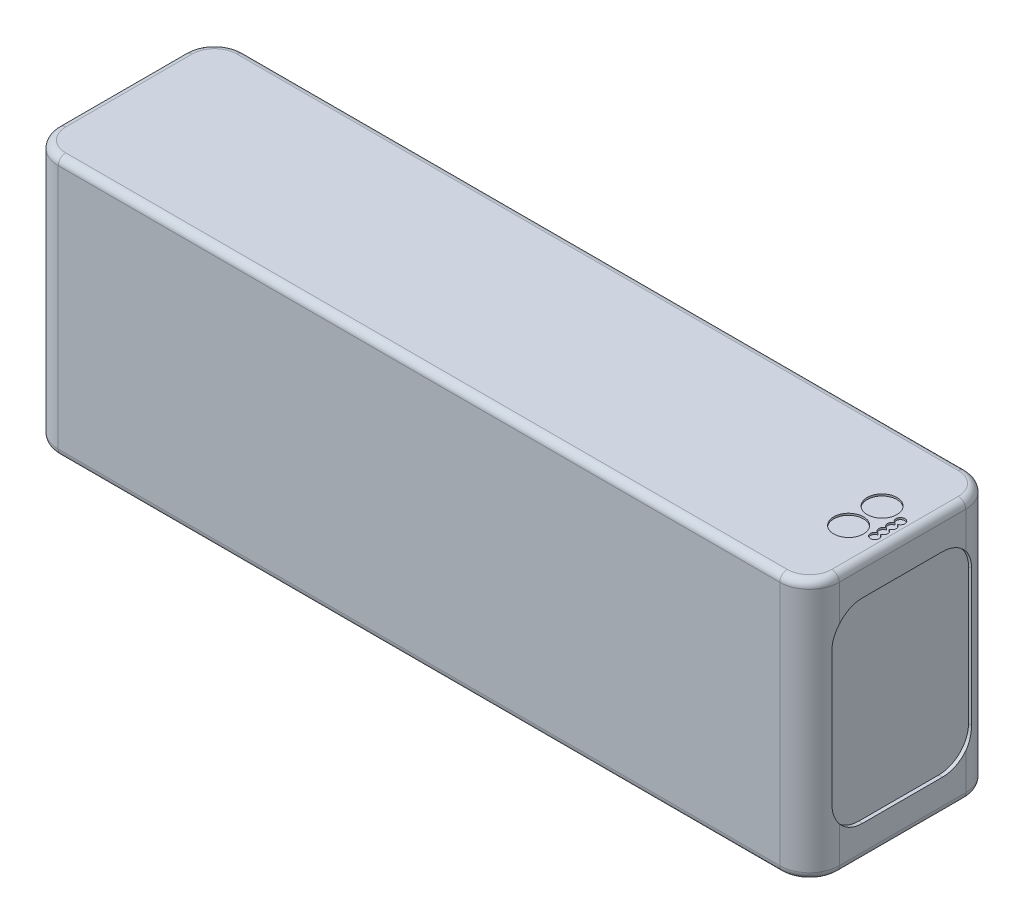
SolidWorks part; units mm, degrees
ref_plane "Front Plane" through (0, 0, 0) normal (0, 0, 1) x (1, 0, 0)
ref_plane "Top Plane" through (0, 0, 0) normal (0, 1, 0) x (1, 0, 0)
ref_plane "Right Plane" through (0, 0, 0) normal (1, 0, 0) x (0, 0, -1)
ref_plane "Plane1" through (0, 0, -15) normal (0, 0, -1) x (-1, 0, 0)
sketch "Sketch1" plane through (0, 0, -15) normal (0, 0, -1) x (-1, 0, 0)
  line L0 (-52.5, -17.5) -> (52.5, -17.5)
  line L1 (52.5, -17.5) -> (52.5, 17.5)
  line L2 (52.5, 17.5) -> (-52.5, 17.5)
  line L3 (-52.5, 17.5) -> (-52.5, -17.5)
  line L4 (-52.5, 0) -> (52.5, 0) construction
  line L5 (0, 17.5) -> (0, -17.5) construction
  dimension "D1" = 35
  dimension "D2" = 105
extrude "Boss-Extrude1" add sketch "Sketch1" against normal blind 25
sketch "Sketch2" plane through (52.5, 0, 0) normal (1, 0, 0) x (0, 0, -1)
  line L0 (-6.875, 9.125) -> (-6.875, -9.125)
  line L1 (-2.875, -13.125) -> (7.875, -13.125)
  line L2 (11.875, -9.125) -> (11.875, 9.125)
  line L3 (7.875, 13.125) -> (-2.875, 13.125)
  line L4 (-10, 17.5) -> (15, -17.5) construction
  line L5 (15, 17.5) -> (-10, -17.5) construction
  line L6 (-6.875, 13.125) -> (11.875, -13.125) construction
  line L7 (11.875, 13.125) -> (-6.875, -13.125) construction
  line L12 (-10, 17.5) -> (15, 17.5) construction
  line L13 (-10, 17.5) -> (-10, -17.5) construction
  line L14 (-10, -17.5) -> (15, -17.5) construction
  line L15 (15, 17.5) -> (15, -17.5) construction
  line L16 (-10, 17.5) -> (15, -17.5) construction
  line L17 (-10, -17.5) -> (15, 17.5) construction
  arc A0 (-6.875, -9.125) -> (-2.875, -13.125) centre (-2.875, -9.125) ccw
  arc A1 (7.875, -13.125) -> (11.875, -9.125) centre (7.875, -9.125) ccw
  arc A2 (11.875, 9.125) -> (7.875, 13.125) centre (7.875, 9.125) ccw
  arc A3 (-6.875, 9.125) -> (-2.875, 13.125) centre (-2.875, 9.125) cw
  point P16 (2.5, 0)
  dimension "D3" = 4
  dimension "D1" = 18.75
  dimension "D2" = 25
extrude "Cut-Extrude1" cut sketch "Sketch2" against normal blind 0.5
sketch "Sketch3" plane through (-52.5, 0, 0) normal (-1, 0, 0) x (0, 0, 1)
  line L0 (2.875, 13.125) -> (-7.875, 13.125)
  line L1 (-11.875, 9.125) -> (-11.875, -9.125)
  line L2 (-7.875, -13.125) -> (2.875, -13.125)
  line L3 (6.875, -9.125) -> (6.875, 9.125)
  line L4 (-11.875, 13.125) -> (6.875, -13.125) construction
  line L5 (6.875, 13.125) -> (-11.875, -13.125) construction
  line L6 (-15, 17.5) -> (10, -17.5) construction
  line L7 (10, -17.5) -> (-15, -17.5) construction
  line L8 (-15, -17.5) -> (10, 17.5) construction
  arc A0 (-11.875, -9.125) -> (-7.875, -13.125) centre (-7.875, -9.125) ccw
  arc A1 (2.875, -13.125) -> (6.875, -9.125) centre (2.875, -9.125) ccw
  arc A2 (2.875, 13.125) -> (6.875, 9.125) centre (2.875, 9.125) cw
  arc A3 (-7.875, 13.125) -> (-11.875, 9.125) centre (-7.875, 9.125) ccw
  dimension "D3" = 4
  dimension "D1" = 18.75
  dimension "D2" = 25
extrude "Cut-Extrude2" cut sketch "Sketch3" against normal blind 0.5
fillet "Fillet1" radius 4 4 edges at (-52.5, 0, -15) (-52.5, 0, 10) (52.5, 0, -15) (52.5, 0, 10) tangent propagation no
fillet "Fillet2" radius 1 16 edges at (51.3284, 17.5, -13.8284) (52.5, 17.5, -2.5) (0, 17.5, -15) (51.3284, 17.5, 8.8284) (-51.3284, 17.5, -13.8284) (0, 17.5, 10) (-52.5, 17.5, -2.5) (-51.3284, 17.5, 8.8284) (-52.5, -17.5, -2.5) (-51.3284, -17.5, -13.8284) (-51.3284, -17.5, 8.8284) (0, -17.5, -15) (0, -17.5, 10) (51.3284, -17.5, -13.8284) (51.3284, -17.5, 8.8284) (52.5, -17.5, -2.5) tangent propagation no
sketch "Sketch4" plane through (0, 0, 10) normal (0, 0, 1) x (1, 0, 0)
  line L0 (-48.5, 0) -> (48.5, 0) construction
  line L1 (-48.5, 16.5) -> (-48.5, -16.5) construction
  line L2 (48.5, -16.5) -> (48.5, 16.5) construction
  line L3 (0, 25.9735) -> (0, -16.5) construction
  line L4 (-48.5, -16.5) -> (48.5, -16.5) construction
  circle A0 centre (0, 0) radius 0.5026
sketch "Sketch5" plane through (0, 17.5, 0) normal (0, 1, 0) x (1, 0, 0)
  line L0 (47.5, -2.5068) -> (47.5, 11.9202) construction
  line L1 (51.5, 2.5) -> (37.3937, 2.5) construction
  line L2 (51.5, -6) -> (51.5, 11) construction
  line L4 (48.5, -10) -> (-48.5, -10) construction
  line L5 (52.5, 11) -> (52.5, -6) construction
  circle A0 centre (47.5, 0.25) radius 2
  circle A1 centre (47.5, 4.75) radius 2
  dimension "D1" = 4
  dimension "D2" = 4
  dimension "D3" = 4.5
  dimension "D4" = 12.5
  dimension "D5" = 2.25
  dimension "D6" = 5
extrude "Cut-Extrude3" cut sketch "Sketch5" against normal blind 0.25 contours A0 | A1
sketch "Sketch6" plane through (0, 17.5, 0) normal (0, 1, 0) x (1, 0, 0)
  line L0 (40.4856, 2.5) -> (50.5, 2.5) construction
  line L1 (-48.5, 15) -> (48.5, 15) construction
  line L2 (50.5, 8.3849) -> (50.5, -5.8297) construction
  line L3 (52.5, 11) -> (52.5, -6) construction
  arc A0 (50.6714, 3.65) -> (50.3286, 3.65) centre (50.5, 4.225) ccw
  arc A1 (50.3286, 3.65) -> (50.3286, 2.5) centre (50.5, 3.075) ccw
  arc A2 (50.3286, 2.5) -> (50.3286, 1.35) centre (50.5, 1.925) ccw
  arc A3 (50.3286, 1.35) -> (50.6714, 1.35) centre (50.5, 0.775) ccw
  arc A4 (50.6714, 2.5) -> (50.6714, 3.65) centre (50.5, 3.075) ccw
  arc A5 (50.6714, 1.35) -> (50.6714, 2.5) centre (50.5, 1.925) ccw
  dimension "D3" = 1.2
  dimension "D4" = 1.15
  dimension "D5" = 1.15
  dimension "D6" = 1.15
  dimension "D7" = 0.575
  dimension "D1" = 12.5
  dimension "D2" = 2
extrude "Cut-Extrude4" cut sketch "Sketch6" against normal blind 0.25
equation "\"D1@Sketch3\"=\"D2@Sketch3\" * .75"
equation "\"D1@Sketch2\"=\"D2@Sketch2\"* .75"
